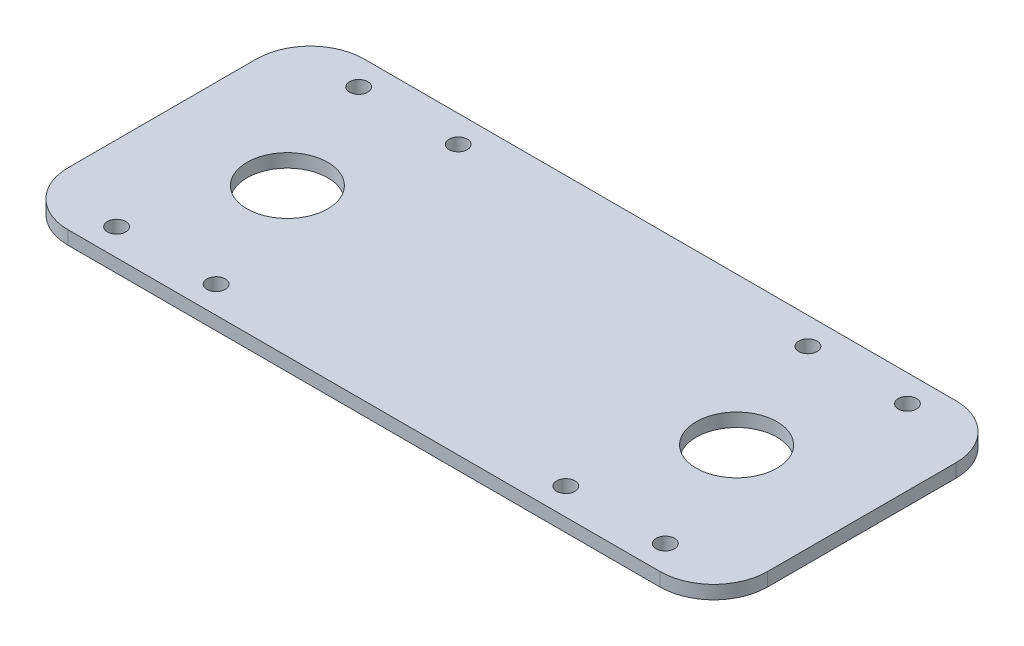
SolidWorks part; units mm, degrees
ref_plane "Front Plane" through (0, 0, 0) normal (0, 0, 1) x (1, 0, 0)
ref_plane "Top Plane" through (0, 0, 0) normal (0, 1, 0) x (1, 0, 0)
ref_plane "Right Plane" through (0, 0, 0) normal (1, 0, 0) x (0, 0, -1)
sketch "Sketch1" plane through (0, 0, 0) normal (0, 1, 0) x (1, 0, 0)
  line L1 (10, 0) -> (120, 0)
  line L2 (0, 10) -> (0, 45)
  line L3 (10, 55) -> (120, 55)
  line L4 (130, 10) -> (130, 45)
  arc A0 (10, 55) -> (0, 45) centre (10, 45) ccw
  arc A1 (0, 10) -> (10, 0) centre (10, 10) ccw
  arc A2 (130, 10) -> (120, 0) centre (120, 10) cw
  arc A3 (120, 55) -> (130, 45) centre (120, 45) cw
  point P7 (0, 55)
  point P10 (0, 0)
  point P13 (130, 0)
  dimension "D3" = 10
  dimension "D4" = 10
  dimension "D5" = 10
  dimension "D6" = 10
  dimension "D1" = 130
  dimension "D2" = 55
extrude "Boss-Extrude1" add sketch "Sketch1" along normal blind 2.5
sketch "Sketch2" plane through (0, 2.5, 0) normal (0, 1, 0) x (1, 0, 0)
  line L0 (0, 45) -> (0, 10) construction
  line L1 (10, 0) -> (120, 0) construction
  line L2 (120, 55) -> (10, 55) construction
  line L3 (65, 55) -> (65, 0) construction
  circle A0 centre (14, 5) radius 1.7
  circle A1 centre (14, 50) radius 1.7
  circle A2 centre (116, 5) radius 1.7
  circle A3 centre (116, 50) radius 1.7
  dimension "D2" = 14
  dimension "D3" = 5
  dimension "D5" = 5
extrude "Cut-Extrude1" cut sketch "Sketch2" against normal through all
sketch "Sketch3" plane through (0, 2.5, 0) normal (0, 1, 0) x (1, 0, 0)
  circle A1 centre (32.5, 50) radius 1.7
  circle A2 centre (32.5, 5) radius 1.7
  circle A3 centre (97.5, 5) radius 1.7
  circle A4 centre (97.5, 50) radius 1.7
extrude "Cut-Extrude2" cut sketch "Sketch3" against normal blind 10
sketch "Sketch4" plane through (0, 2.5, 0) normal (0, 1, 0) x (1, 0, 0)
  line L0 (65, 55) -> (65, 0) construction
  line L1 (120, 55) -> (10, 55) construction
  line L2 (10, 0) -> (120, 0) construction
  circle A0 centre (23.25, 27.5) radius 7.5
  circle A1 centre (106.75, 27.5) radius 7.5
extrude "Cut-Extrude3" cut sketch "Sketch4" against normal blind 10
sketch "Sketch5" plane through (0, 0, 0) normal (0, -1, 0) x (1, 0, 0)
  line L0 (32.5, -5) -> (97.5, -5)
  line L1 (97.5, -5) -> (97.5, -50)
